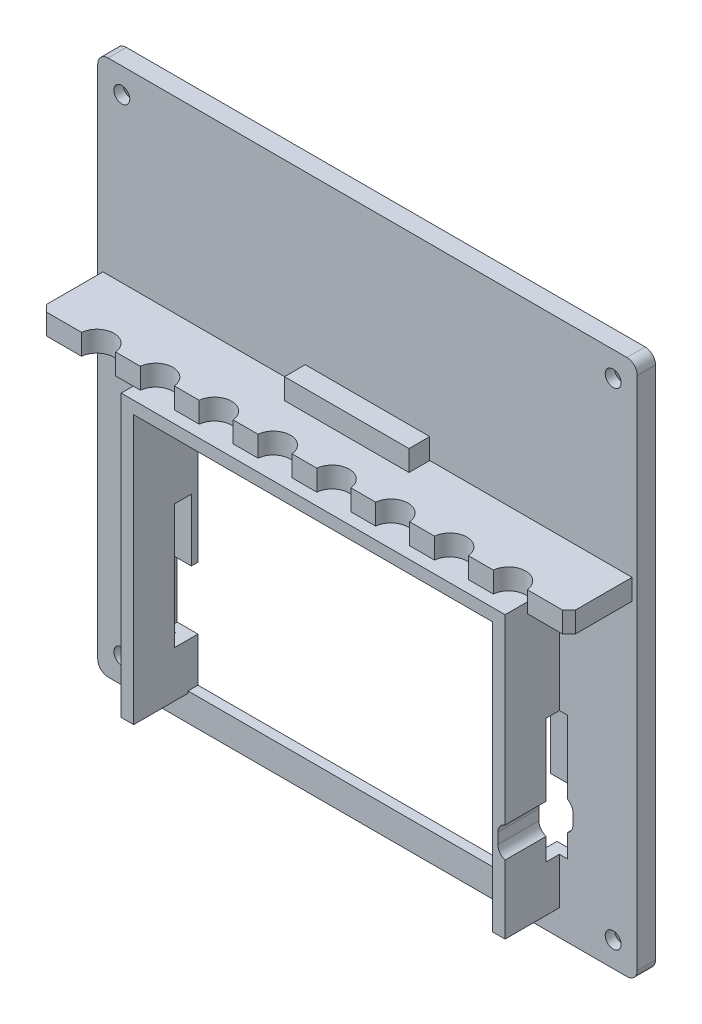
SolidWorks part; units mm, degrees
ref_plane "Front Plane" through (0, 0, 0) normal (0, 0, 1) x (1, 0, 0)
ref_plane "Top Plane" through (0, 0, 0) normal (0, 1, 0) x (1, 0, 0)
ref_plane "Right Plane" through (0, 0, 0) normal (1, 0, 0) x (0, 0, -1)
sketch "Sketch1" plane through (0, 0, 0) normal (0, 0, 1) x (1, 0, 0)
  line L0 (0, 100.111) -> (0, -6.1494) construction
  line L1 (-41.529, -41.275) -> (41.529, -41.275)
  line L2 (-41.529, -41.275) -> (-41.529, 41.275)
  line L3 (-41.529, 41.275) -> (41.529, 41.275)
  line L4 (41.529, -41.275) -> (41.529, 41.275)
  line L5 (41.529, 0) -> (-41.529, 0) construction
  line L6 (0, -55) -> (0, 55) construction
  line L7 (55, 0) -> (-55, 0) construction
  dimension "D1" = 83.058
  dimension "D2" = 82.55
extrude "Boss-Extrude1" add sketch "Sketch1" along normal blind 2.794
sketch "Sketch2" plane through (0, 0, 0) normal (0, 0, -1) x (-1, 0, 0)
  line L0 (0, 41.275) -> (0, -41.275) construction
  line L1 (-29.3687, 5.9309) -> (29.3688, 5.9309)
  line L2 (-29.3687, 5.9309) -> (-29.3687, -37.0586)
  line L3 (-29.3687, -37.0586) -> (29.3688, -37.0586)
  line L4 (29.3688, 5.9309) -> (29.3688, -37.0586)
  line L5 (-41.529, 41.275) -> (41.529, 41.275) construction
  line L6 (41.529, -41.275) -> (-41.529, -41.275) construction
  line L7 (-27.4637, 4.0259) -> (27.4638, 4.0259)
  line L8 (27.4638, 4.0259) -> (27.4638, -35.1536)
  line L9 (-27.4637, -35.1536) -> (27.4638, -35.1536)
  line L10 (-27.4637, 4.0259) -> (-27.4637, -35.1536)
  line L11 (-27.4637, -15.5639) -> (27.4638, -15.5639) construction
  line L20 (29.3688, 5.9309) -> (29.3688, -37.0586) construction
  line L22 (-29.3687, 5.9309) -> (-29.3687, -37.0586) construction
  dimension "D1" = 42.9895
  dimension "D2" = 58.7375
  dimension "D3" = 4.2164
  dimension "D4" = 1.905
extrude "Boss-Extrude2" add sketch "Sketch2" against normal blind 11.1125
sketch "Sketch5" plane through (0, 0, 0) normal (0, 0, -1) x (-1, 0, 0)
  line L4 (33.4645, 8.128) -> (-33.4645, 8.128)
  line L5 (-33.4645, 8.128) -> (-33.4645, -41.275)
  line L7 (33.4645, -41.275) -> (33.4645, 8.128)
  line L8 (0, 41.275) -> (0, -41.275) construction
  line L9 (-41.529, 41.275) -> (41.529, 41.275) construction
  line L10 (41.529, -41.275) -> (-41.529, -41.275) construction
  line L11 (33.4645, -41.275) -> (-33.4645, -41.275)
  dimension "D1" = 49.403
  dimension "D2" = 66.929
extrude "Cut-Extrude1" cut sketch "Sketch5" against normal blind 1.27
extrude "Cut-Extrude2" cut sketch "Sketch2<2>" against normal through all contours L7 L8 L9 L10
sketch "Sketch2<2>" plane through (0, 0, 0) normal (0, 0, -1) x (-1, 0, 0) same geometry as "Sketch2"
hole_wizard "CSK for #2 Flat Head Machine Screw1" positions "Sketch6" profile "Sketch7" countersink size "#2" standard "ANSI Inch" end condition through all
sketch "Sketch6" plane through (0, 0, 0) normal (0, 0, -1) x (-1, 0, 0)
  point P0 (37.592, 37.211)
  point P3 (-37.592, 37.211)
  point P6 (-37.592, -37.211)
  point P9 (37.592, -37.211)
  dimension "D1" = 37.211
  dimension "D2" = 37.211
  dimension "D3" = 37.592
  dimension "D4" = 75.184
sketch "Sketch7" plane through (-37.592, 37.211, 0) normal (1, 0, 0) x (0, 1, 0)
  line L0 (0, 0) -> (0, 11.1125)
  line L1 (0, 11.1125) -> (1.2192, 11.1125)
  line L2 (1.2192, 11.1125) -> (1.2192, 1.3643)
  line L3 (1.2192, 1.3643) -> (2.4052, 0)
  line L5 (2.4052, 0) -> (0, 0)
  line L6 (-1.2192, 1.3643) -> (-2.4052, 0) construction
  line L11 (0, -6.35) -> (0, 107.95) construction
  dimension "Thru Hole Dia." = 2.4384
  dimension "Thru Hole Depth" = 11.1125
  dimension "Near C'Sink Dia." = 4.8104
  dimension "Near C'Sink Angle" = 82
sketch "Sketch9" plane through (0, 4.0259, 0) normal (0, -1, 0) x (1, 0, 0)
  line L1 (-6.35, 3.81) -> (6.35, 3.81)
  line L2 (-6.35, 3.81) -> (-6.35, 1.27)
  line L3 (-6.35, 1.27) -> (6.35, 1.27)
  line L4 (6.35, 3.81) -> (6.35, 1.27)
  line L5 (-6.35, 3.81) -> (6.35, 1.27) construction
  line L6 (-6.35, 1.27) -> (6.35, 3.81) construction
  line L8 (-33.4645, 1.27) -> (33.4645, 1.27) construction
  point P0 (0, 2.54)
  dimension "D1" = 12.7
  dimension "D2" = 2.54
extrude "Cut-Extrude4" cut sketch "Sketch9" against normal blind 9.8044
sketch "Sketch10" plane through (0, 0, 1.27) normal (0, 0, 1) x (1, 0, 0)
  line L0 (6.35, 13.8303) -> (6.35, 8.128) construction
  line L1 (-6.35, 13.8303) -> (6.35, 13.8303)
  line L2 (-6.35, 13.8303) -> (-6.35, 10.7823)
  line L3 (-6.35, 10.7823) -> (6.35, 10.7823)
  line L4 (6.35, 13.8303) -> (6.35, 10.7823)
  dimension "D1" = 3.048
extrude "Cut-Extrude5" cut sketch "Sketch10" against normal blind 0.254
sketch "Sketch11" plane through (0, 0, 1.27) normal (0, 0, -1) x (-1, 0, 0)
  line L0 (-27.4637, 4.0259) -> (-27.4637, -35.1536) construction
  line L1 (-27.4637, -20.447) -> (-30.6387, -20.447)
  line L2 (-27.4637, -20.447) -> (-27.4637, -29.972)
  line L3 (-27.4637, -29.972) -> (-30.6387, -29.972)
  line L4 (-30.6387, -20.447) -> (-30.6387, -29.972)
  line L5 (-6.35, 8.128) -> (-33.4645, 8.128) construction
  dimension "D1" = 9.525
  dimension "D2" = 3.175
  dimension "D3" = 28.575
extrude "Cut-Extrude7" cut sketch "Sketch11" against normal up to surface (1.524 mm away) up to face at (-38.8112, 37.211, 2.794)
sketch "Sketch12" plane through (27.4637, 0, 0) normal (-1, 0, 0) x (0, 0, 1)
  line L0 (2.794, -20.447) -> (1.27, -20.447) construction
  line L1 (2.794, -29.972) -> (4.826, -29.972)
  line L2 (2.794, -29.972) -> (2.794, -10.922)
  line L3 (2.794, -10.922) -> (4.826, -10.922)
  line L4 (4.826, -29.972) -> (4.826, -10.922)
  dimension "D1" = 2.032
  dimension "D2" = 9.525
extrude "Cut-Extrude8" cut sketch "Sketch12" against normal through all
sketch "Sketch14" plane through (0, 0, 2.794) normal (0, 0, 1) x (1, 0, 0)
  line L1 (30.6387, -29.972) -> (27.4637, -29.972)
  line L2 (30.6387, -29.972) -> (30.6387, -10.922)
  line L3 (30.6387, -10.922) -> (27.4637, -10.922)
  line L4 (27.4637, -29.972) -> (27.4637, -10.922)
extrude "Cut-Extrude11" cut sketch "Sketch14" against normal blind 0.508
mirror "Mirror1" about plane through (0, 0, 0) normal (1, 0, 0) of "Cut-Extrude11", "Cut-Extrude8", "Cut-Extrude7"
fillet "Fillet2" radius 4.7625 2 edges at (-33.4645, 8.128, 0.635) (33.4645, 8.128, 0.635)
sketch "Sketch15" plane through (0, 0, 11.1125) normal (0, 0, 1) x (1, 0, 0)
  line L0 (29.3687, -37.0586) -> (-29.3688, -37.0586) construction
  line L1 (-27.4638, -35.1536) -> (27.4637, -35.1536)
  line L2 (-27.4638, -35.1536) -> (-27.4638, -37.0586)
  line L3 (-27.4638, -37.0586) -> (27.4637, -37.0586)
  line L4 (27.4637, -35.1536) -> (27.4637, -37.0586)
  line L5 (27.4637, 4.0259) -> (27.4637, -35.1536) construction
extrude "Cut-Extrude12" cut sketch "Sketch15" against normal up to surface (8.3185 mm away) up to face at (-38.8112, -37.211, 2.794)
sketch "Sketch16" plane through (0, -35.1536, 0) normal (0, 1, 0) x (1, 0, 0)
  line L4 (-27.4638, -1.27) -> (-27.4638, -2.794)
  line L5 (-27.4638, -2.794) -> (27.4637, -2.794)
  line L6 (27.4637, -2.794) -> (27.4637, -1.27)
  line L7 (27.4637, -1.27) -> (-27.4638, -1.27)
  line L8 (-27.4638, -1.27) -> (-27.4638, -2.794)
  line L9 (-27.4638, -2.794) -> (27.4637, -2.794)
  line L10 (27.4637, -2.794) -> (27.4637, -1.27)
  line L11 (27.4637, -1.27) -> (-27.4638, -1.27)
  dimension "D1" = 0
extrude "Cut-Extrude13" cut sketch "Sketch16" against normal blind 1.5875
sketch "Sketch17" plane through (0, 0, 1.27) normal (0, 0, 1) x (1, 0, 0)
  line L4 (6.35, 8.128) -> (6.35, 10.7823)
  line L5 (6.35, 10.7823) -> (-6.35, 10.7823)
  line L6 (-6.35, 10.7823) -> (-6.35, 8.128)
  line L7 (-6.35, 8.128) -> (6.35, 8.128)
  line L8 (6.35, 8.128) -> (6.35, 10.7823)
  line L9 (6.35, 10.7823) -> (-6.35, 10.7823)
  line L10 (-6.35, 10.7823) -> (-6.35, 8.128)
  line L11 (-6.35, 8.128) -> (6.35, 8.128)
  dimension "D1" = 0
extrude "Boss-Extrude3" add sketch "Sketch17" along normal blind 0.1016
sketch "Sketch18" plane through (0, 10.7823, 0) normal (0, 1, 0) x (1, 0, 0)
  line L4 (-6.35, -1.016) -> (-6.35, -1.3716)
  line L5 (-6.35, -1.3716) -> (6.35, -1.3716)
  line L6 (6.35, -1.3716) -> (6.35, -1.016)
  line L7 (6.35, -1.016) -> (-6.35, -1.016)
  line L8 (-6.35, -1.016) -> (-6.35, -1.3716)
  line L9 (-6.35, -1.3716) -> (6.35, -1.3716)
  line L10 (6.35, -1.3716) -> (6.35, -1.016)
  line L11 (6.35, -1.016) -> (-6.35, -1.016)
  dimension "D1" = 0
extrude "Cut-Extrude14" cut sketch "Sketch18" against normal blind 0.1016
sketch "Sketch19" plane through (0, 0, 0) normal (0, 0, -1) x (-1, 0, 0)
  line L0 (-41.529, 41.275) -> (41.529, 41.275) construction
  line L1 (-41.275, 41.021) -> (41.275, 41.021)
  line L2 (-41.275, 41.021) -> (-41.275, -41.021)
  line L4 (41.275, 41.021) -> (41.275, -41.021)
  line L5 (41.529, 41.275) -> (41.529, -41.275) construction
  line L6 (-41.275, -41.021) -> (41.275, -41.021)
  line L7 (-41.529, -41.275) -> (-41.529, 41.275) construction
  line L9 (41.529, -41.275) -> (-41.529, -41.275) construction
  line L10 (-80.7469, 66.9735) -> (80.7469, 66.9735)
  line L11 (-80.7469, 66.9735) -> (-80.7469, -66.9735)
  line L12 (-80.7469, -66.9735) -> (80.7469, -66.9735)
  line L13 (80.7469, 66.9735) -> (80.7469, -66.9735)
  line L14 (-80.7469, 66.9735) -> (80.7469, -66.9735) construction
  line L15 (-80.7469, -66.9735) -> (80.7469, 66.9735) construction
  point P0 (0, 0)
  point P14 (0, 0)
  dimension "D1" = 0.254
  dimension "D2" = 0.254
  dimension "D3" = 0.254
  dimension "D4" = 0.254
  dimension "D5" = 25.9525
  dimension "D6" = 39.4719
extrude "Cut-Extrude15" cut sketch "Sketch19" against normal through all
fillet "Fillet3" radius 1.5875 4 edges at (-41.275, 41.021, 1.397) (41.275, 41.021, 1.397) (-41.275, -41.021, 1.397) (41.275, -41.021, 1.397)
sketch "Sketch21" plane through (0, 0, 2.794) normal (0, 0, 1) x (1, 0, 0)
  line L0 (-29.3688, 5.9309) -> (-6.35, 5.9309) construction
  line L1 (40.4812, 12.2809) -> (-40.4812, 12.2809)
  line L2 (40.4812, 12.2809) -> (40.4812, 9.1059)
  line L3 (40.4812, 9.1059) -> (-40.4812, 9.1059)
  line L4 (-40.4812, 12.2809) -> (-40.4812, 9.1059)
  dimension "D1" = 3.175
  dimension "D2" = 80.9625
  dimension "D3" = 40.4812
  dimension "D4" = 3.175
extrude "Boss-Extrude4" add sketch "Sketch21" along normal blind 9.906
sketch "Sketch22" plane through (0, 0, 2.794) normal (0, 0, 1) x (1, 0, 0)
  line L0 (6.35, 5.9309) -> (29.3687, 5.9309) construction
  line L1 (-9.525, 15.4559) -> (9.525, 15.4559)
  line L2 (-9.525, 15.4559) -> (-9.525, 5.9309)
  line L3 (-9.525, 5.9309) -> (9.525, 5.9309)
  line L4 (9.525, 15.4559) -> (9.525, 5.9309)
  line L5 (-29.3688, 5.9309) -> (-6.35, 5.9309) construction
  dimension "D1" = 9.525
  dimension "D2" = 9.525
  dimension "D3" = 9.525
extrude "Boss-Extrude5" add sketch "Sketch22" along normal blind 3.175
sketch "Sketch23" plane through (0, 5.9309, 0) normal (0, -1, 0) x (1, 0, 0)
  line L4 (-6.35, 2.794) -> (6.35, 2.794)
  line L5 (6.35, 2.794) -> (6.35, 3.81)
  line L6 (6.35, 3.81) -> (-6.35, 3.81)
  line L7 (-6.35, 3.81) -> (-6.35, 2.794)
  line L8 (-6.35, 2.794) -> (6.35, 2.794)
  line L9 (6.35, 2.794) -> (6.35, 3.81)
  line L10 (6.35, 3.81) -> (-6.35, 3.81)
  line L11 (-6.35, 3.81) -> (-6.35, 2.794)
  dimension "D1" = 0
extrude "Cut-Extrude16" cut sketch "Sketch23" against normal up to surface (7.8994 mm away) up to face at (0, 13.8303, 1.905)
sketch "Sketch24" plane through (0, 9.1059, 0) normal (0, -1, 0) x (1, 0, 0)
  circle A0 centre (-31.5, 12.7) radius 2.6098 construction
  circle A1 centre (-31.5, 12.7) radius 2.6098
  circle A2 centre (-22.5, 12.7) radius 2.6099 construction
  circle A3 centre (-22.5, 12.7) radius 2.6098
  circle A4 centre (31.5, 12.7) radius 2.6099 construction
  circle A5 centre (22.5, 12.7) radius 2.6099 construction
  circle A6 centre (13.5, 12.7) radius 2.6098 construction
  circle A7 centre (4.5, 12.7) radius 2.6098 construction
  circle A8 centre (-4.5, 12.7) radius 2.6099 construction
  circle A9 centre (-13.5, 12.7) radius 2.6099 construction
  circle A10 centre (31.5, 12.7) radius 2.6099
  circle A11 centre (22.5, 12.7) radius 2.6098
  circle A12 centre (13.5, 12.7) radius 2.6098
  circle A13 centre (4.5, 12.7) radius 2.6098
  circle A14 centre (-4.5, 12.7) radius 2.6098
  circle A15 centre (-13.5, 12.7) radius 2.6098
extrude "Cut-Extrude17" cut sketch "Sketch24" against normal through all
sketch "Sketch25" plane through (0, 0, 12.7) normal (0, 0, 1) x (1, 0, 0)
  line L1 (-40.4812, 12.2809) -> (40.4812, 12.2809)
  line L2 (-40.4812, 12.2809) -> (-40.4812, 9.1059)
  line L3 (-40.4812, 9.1059) -> (40.4812, 9.1059)
  line L4 (40.4812, 12.2809) -> (40.4812, 9.1059)
extrude "Cut-Extrude18" cut sketch "Sketch25" against normal blind 0.254
chamfer "Chamfer1" distance 1.016 angle 45 2 edges at (-40.4812, 10.6934, 12.446) (40.4812, 10.6934, 12.446)
sketch "Sketch26" plane through (0, 0, 1.27) normal (0, 0, -1) x (-1, 0, 0)
  line L2 (-29.845, -23.4506) -> (-29.845, -25.0635) construction
  line L3 (-28.2575, -23.4506) -> (-28.2575, -25.0635)
  line L4 (-31.4325, -23.4506) -> (-31.4325, -25.0635)
  arc A1 (-28.2575, -23.4506) -> (-31.4325, -23.4506) centre (-29.845, -23.4506) ccw
  arc A2 (-31.4325, -25.0635) -> (-28.2575, -25.0635) centre (-29.845, -25.0635) ccw
  point P8 (-29.845, -24.257)
  dimension "D2" = 1.6129
  dimension "D4" = 1.5875
  dimension "D1" = 24.257
extrude "Cut-Extrude19" cut sketch "Sketch26" against normal through all
sketch "Sketch29" plane through (0, 0, 1.27) normal (0, 0, -1) x (-1, 0, 0)
  line L0 (28.702, 8.128) -> (6.35, 8.128) construction
  line L1 (-27.4637, 4.0259) -> (27.4638, 4.0259)
  line L2 (-27.4637, 4.0259) -> (-27.4637, 8.128)
  line L3 (-27.4637, 8.128) -> (27.4638, 8.128)
  line L4 (27.4638, 4.0259) -> (27.4638, 8.128)
  line L5 (27.4638, 4.0259) -> (27.4637, -20.447) construction
extrude "Cut-Extrude20" cut sketch "Sketch29" against normal blind 0.381
chamfer "Chamfer2" distance 0.508 2 edges at (16.9069, 4.0259, 1.651) (-16.9069, 4.0259, 1.651)
